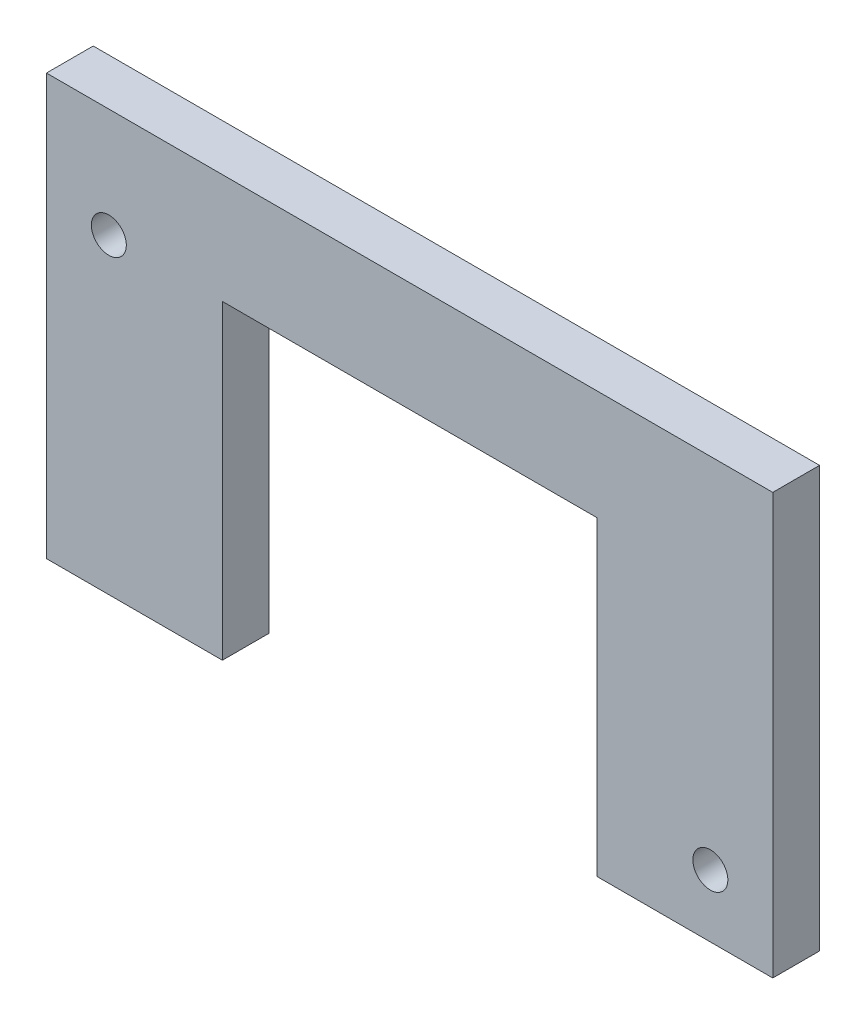
SolidWorks part; units mm, degrees
ref_plane "Front Plane" through (0, 0, 0) normal (0, 0, 1) x (1, 0, 0)
ref_plane "Top Plane" through (0, 0, 0) normal (0, 1, 0) x (1, 0, 0)
ref_plane "Right Plane" through (0, 0, 0) normal (1, 0, 0) x (0, 0, -1)
sketch "Sketch1" plane through (0, 0, 0) normal (0, 0, 1) x (1, 0, 0)
  line L1 (0, 0) -> (33.782, 0) construction
  line L2 (0, 0) -> (0, 19.812) construction
  line L3 (0, 19.812) -> (33.782, 19.812) construction
  line L4 (33.782, 0) -> (33.782, 19.812) construction
  line L5 (-1.5875, -1.5875) -> (35.3695, -1.5875)
  line L6 (-1.5875, -1.5875) -> (-1.5875, 19.812)
  line L7 (-1.5875, 19.812) -> (35.3695, 19.812)
  line L8 (35.3695, -1.5875) -> (35.3695, 19.812)
  circle A0 centre (1.5875, 14.2558) radius 0.889
  circle A1 centre (32.1945, 1.5875) radius 0.889
  dimension "D3" = 1.778
  dimension "D4" = 1.778
  dimension "D5" = 1.5875
  dimension "D6" = 1.5875
  dimension "D7" = 1.5875
  dimension "D8" = 5.5562
  dimension "D9" = 3.175
  dimension "D11" = 3.175
  dimension "D12" = 5.5562
  dimension "D1" = 19.812
  dimension "D2" = 33.782
  dimension "D10" = 3.175
extrude "Boss-Extrude1" add sketch "Sketch1" along normal blind 2.3813
sketch "Sketch2" plane through (0, 0, 2.3813) normal (0, 0, 1) x (1, 0, 0)
  line L5 (-1.5875, -1.5875) -> (35.3695, -1.5875) construction
  line L6 (7.366, -1.5875) -> (26.416, -1.5875)
  line L7 (7.366, -1.5875) -> (7.366, 14.224)
  line L8 (7.366, 14.224) -> (26.416, 14.224)
  line L9 (26.416, -1.5875) -> (26.416, 14.224)
  line L10 (-1.5875, -1.5875) -> (7.366, -1.5875) construction
  line L11 (26.416, -1.5875) -> (35.3695, -1.5875) construction
  line L12 (35.3695, 19.812) -> (-1.5875, 19.812) construction
  dimension "D1" = 19.05
  dimension "D2" = 5.588
extrude "Cut-Extrude1" cut sketch "Sketch2" against normal up to next
